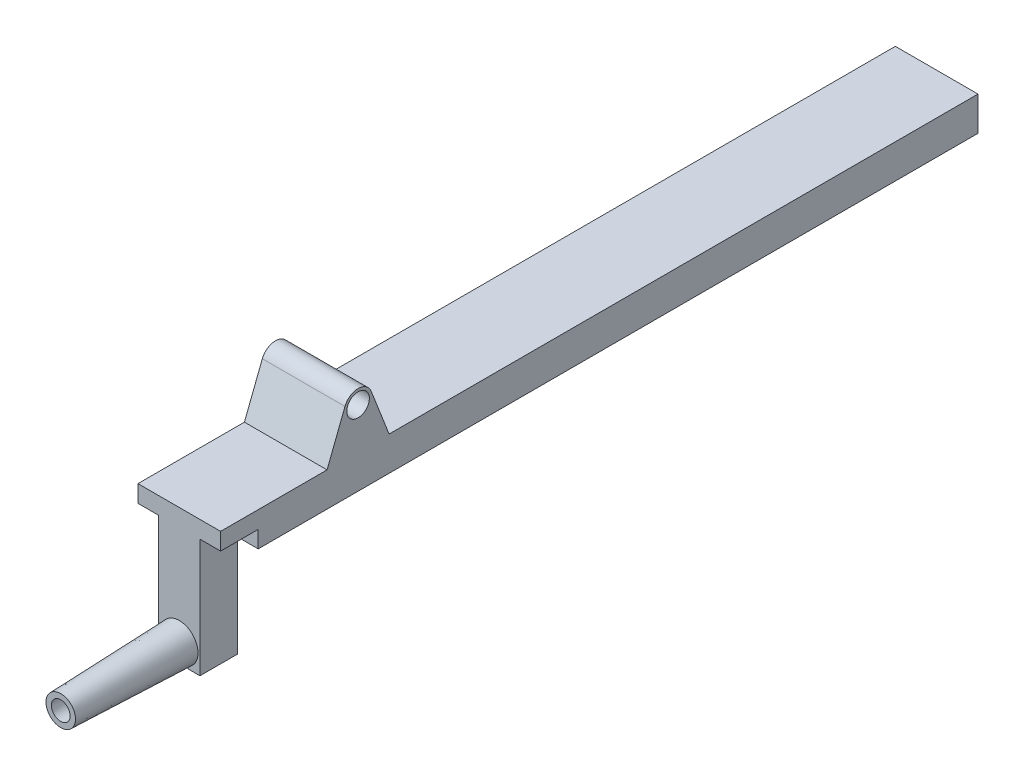
SolidWorks part; units mm, degrees
ref_plane "Front Plane" through (0, 0, 0) normal (0, 0, 1) x (1, 0, 0)
ref_plane "Top Plane" through (0, 0, 0) normal (0, 1, 0) x (1, 0, 0)
ref_plane "Right Plane" through (0, 0, 0) normal (1, 0, 0) x (0, 0, -1)
sketch "Sketch3" plane through (0, 0, 0) normal (1, 0, 0) x (0, 0, -1)
  line L1 (28.9563, -27.6098) -> (419.112, -27.6098) construction
  line L3 (419.112, -27.6098) -> (28.9563, -27.6098)
  line L4 (419.112, -27.6098) -> (419.112, -39.1795)
  line L5 (419.112, -39.1795) -> (-92.952, -39.1795)
  line L6 (-92.952, -27.6098) -> (-92.952, -39.1795)
  line L7 (0, 0) -> (0, -27.6098) construction
  line L9 (-28.959, -27.6098) -> (-92.952, -27.6098)
  line L10 (0, -27.6098) -> (-20.9804, -27.6098) construction
  line L12 (20.9804, -27.6098) -> (28.9563, -27.6098)
  line L13 (-28.959, -27.6098) -> (-20.9804, -27.6098)
  line L14 (-20.9804, -27.6098) -> (-8.8751, 3.4581)
  line L15 (20.9804, -27.6098) -> (8.8751, 3.4581)
  arc A0 (8.8751, 3.4581) -> (-8.8751, 3.4581) centre (0, 0) ccw
  circle A3 centre (0, 0) radius 7.62
  dimension "D1" = 512.064
  dimension "D3" = 27.6098
  dimension "D5" = 7.9786
  dimension "D2" = 63.993
  dimension "D4" = 11.5697
extrude "Boss-Extrude2" add sketch "Sketch3" along normal blind 27.94 and the other way blind 27.94
sketch "Sketch4" plane through (0, -39.1795, 0) normal (0, -1, 0) x (1, 0, 0)
  line L2 (0, 92.952) -> (0, 80.252) construction
  line L3 (-27.94, 92.952) -> (27.94, 92.952) construction
  line L5 (-13.97, 67.552) -> (13.97, 67.552)
  line L6 (-13.97, 67.552) -> (-13.97, 92.952)
  line L7 (-13.97, 92.952) -> (13.97, 92.952)
  line L8 (13.97, 67.552) -> (13.97, 92.952)
  line L9 (-13.97, 67.552) -> (13.97, 92.952) construction
  line L10 (-13.97, 92.952) -> (13.97, 67.552) construction
extrude "Boss-Extrude3" add sketch "Sketch4" along normal blind 80.01
sketch "Sketch5" plane through (0, 0, 67.552) normal (0, 0, -1) x (-1, 0, 0)
  line L2 (13.97, -119.1895) -> (-13.97, -119.1895) construction
  line L4 (6.0284, -117.6675) -> (6.0284, -119.1895)
  line L5 (6.0284, -119.1895) -> (0, -119.1895)
  line L6 (0, -116.459) -> (0, -96.52)
  arc A0 (0, -119.1895) -> (6.0284, -117.6675) centre (0, -106.4895) ccw
  arc A1 (0, -116.459) -> (0, -96.52) centre (0, -106.4895) ccw
extrude "Cut-Extrude4" cut sketch "Sketch5" against normal up to surface (25.4 mm away) up to face at (0, -56.2896, 92.952)
mirror "Mirror1" about plane through (0, -116.459, 115.2445) normal (1, 0, 0) of "Cut-Extrude4"
sketch "Sketch7" plane through (0, 0, 0) normal (1, 0, 0) x (0, 0, -1)
  line L0 (0, 0) -> (-173.1004, 0) construction
  line L2 (-92.952, -106.426) -> (-173.1004, -106.426) construction
  line L3 (-92.952, -119.1895) -> (-92.952, -39.1795) construction
  line L4 (-173.1004, -106.426) -> (-173.1004, 0) construction
ref_plane "Plane1" through (0, 0, 173.1004) normal (0, 0, 1) x (1, 0, 0)
sketch "Sketch9" plane through (0, 0, 173.1004) normal (0, 0, 1) x (1, 0, 0)
  circle A1 centre (0, -106.4895) radius 9.9695
sketch "Sketch10" plane through (0, 0, 92.952) normal (0, 0, 1) x (1, 0, 0)
  circle A1 centre (0, -106.4895) radius 12.7
loft "Loft1" add profiles "Sketch9", "Sketch10" connector at (9.9695, -106.4895, 173.1004) connector at (12.7, -106.4895, 92.952)
sketch "Sketch11" plane through (0, 0, 92.952) normal (0, 0, 1) x (1, 0, 0)
  circle A0 centre (0, -106.4895) radius 9.9695
sketch "Sketch12" plane through (0, 0, 173.1004) normal (0, 0, 1) x (1, 0, 0)
  circle A0 centre (0, -106.4895) radius 6.35
loft "Cut-Loft1" cut profiles "Sketch11", "Sketch12" connector at (9.9695, -106.4895, 92.952) connector at (6.35, -106.4895, 173.1004)
ref_axis "Axis1" through (-27.94, 0, 0) along (1, 0, 0)
sketch "Sketch14" plane through (0, -39.1795, 0) normal (0, -1, 0) x (1, 0, 0)
  line L0 (-27.94, 67.552) -> (27.94, 67.552)
  line L1 (-27.94, 92.952) -> (-27.94, -419.112) construction
  line L2 (27.94, 92.952) -> (27.94, -419.112) construction
  line L3 (27.94, 67.552) -> (27.94, -419.112)
  line L4 (27.94, -419.112) -> (-27.94, -419.112)
  line L5 (-27.94, -419.112) -> (-27.94, 67.552)
extrude "Boss-Extrude5" add sketch "Sketch14" along normal blind 11.43
ref_point "Point1"
